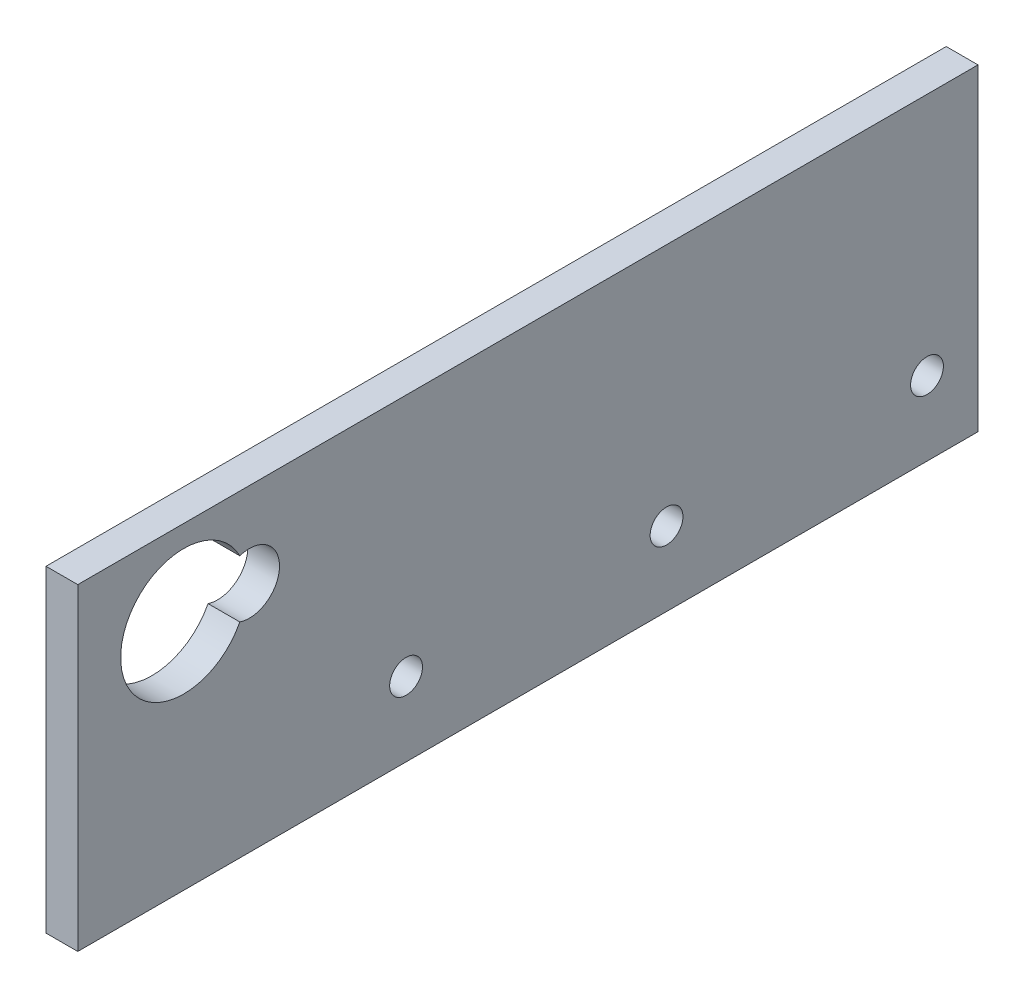
SolidWorks part; units mm, degrees
ref_plane "Ebene vorne" through (0, 0, 0) normal (0, 0, 1) x (1, 0, 0)
ref_plane "Ebene oben" through (0, 0, 0) normal (0, 1, 0) x (1, 0, 0)
ref_plane "Ebene rechts" through (0, 0, 0) normal (1, 0, 0) x (0, 0, -1)
sketch "Skizze1" plane through (0, 0, 0) normal (1, 0, 0) x (0, 0, -1)
  line L1 (0, 0) -> (85, 0)
  line L2 (0, 0) -> (0, 30)
  line L3 (0, 30) -> (85, 30)
  line L4 (85, 0) -> (85, 30)
  dimension "D1" = 85
  dimension "D2" = 30
extrude "Aufsatz-Linear austragen1" add sketch "Skizze1" along normal blind 3
sketch "Skizze2" plane through (3, 0, 0) normal (1, 0, 0) x (0, 0, -1)
  line L0 (10, 0) -> (10, 22) construction
  line L1 (0, 0) -> (85, 0) construction
  line L2 (31, 0) -> (31, 7) construction
  line L3 (55.5919, 0) -> (55.5919, 7) construction
  line L4 (80.1837, 0) -> (80.1837, 7) construction
  line L5 (80.1837, 7) -> (55.5919, 7) construction
  line L6 (55.5919, 7) -> (31, 7) construction
  line L7 (0, 30) -> (0, 0) construction
  circle A0 centre (10, 22) radius 1.55
  circle A1 centre (31, 7) radius 1.55
  circle A2 centre (55.5919, 7) radius 1.55
  circle A3 centre (80.1837, 7) radius 1.55
  dimension "D6" = 3.1
  dimension "D1" = 21
  dimension "D3" = 15
  dimension "D4" = 7
  dimension "D5" = 10
  dimension "D7" = 49.1837
extrude "Bohrungen" cut sketch "Skizze2" against normal through all
sketch "Skizze6" plane through (0, 0, 0) normal (-1, 0, 0) x (0, 0, 1)
  line L0 (-10, 22) -> (0, 22) construction
  line L1 (0, -1.65) -> (0, 1.65) construction
  line L2 (-10, 22) -> (-16.2, 22) construction
  arc A0 (-15.3, 19.2958) -> (-15.3, 24.7042) centre (-10, 22) ccw
  arc A1 (-15.3, 24.7042) -> (-15.3, 19.2958) centre (-16.2, 22) ccw
  dimension "D1" = 11.9
  dimension "D2" = 5.7
  dimension "D3" = 6.2
extrude "Schnitt-Linear austragen3" cut sketch "Skizze6" against normal up to surface (3 mm away) up to face at (3, 22, -11.55)
